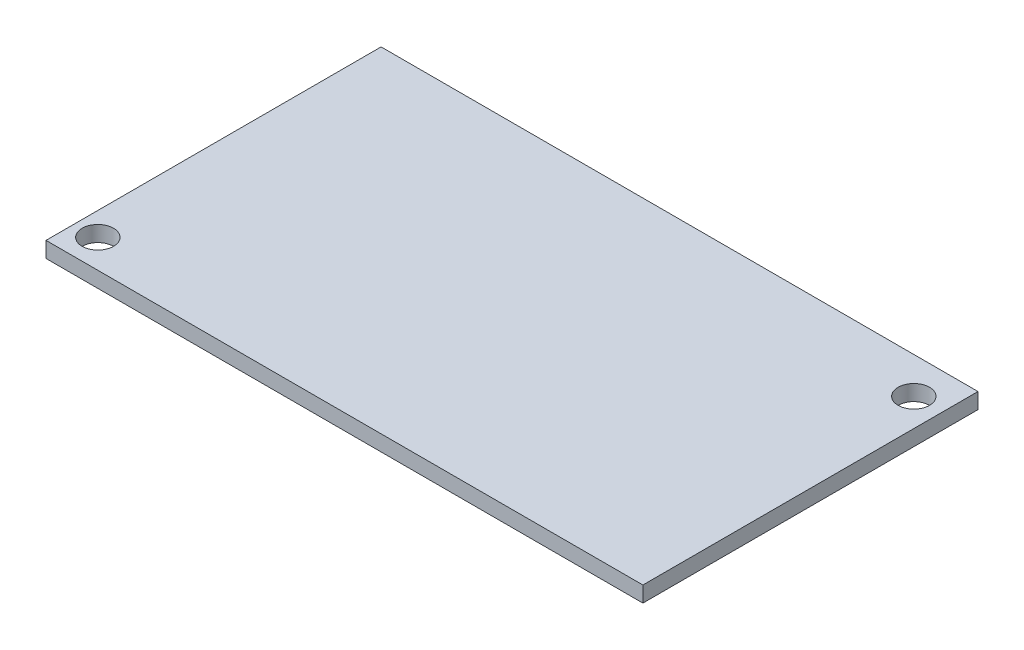
SolidWorks part; units mm, degrees
ref_plane "Front Plane" through (0, 0, 0) normal (0, 0, 1) x (1, 0, 0)
ref_plane "Top Plane" through (0, 0, 0) normal (0, 1, 0) x (1, 0, 0)
ref_plane "Right Plane" through (0, 0, 0) normal (1, 0, 0) x (0, 0, -1)
sketch "Sketch1" plane through (0, 0, 0) normal (0, 1, 0) x (1, 0, 0)
  line L1 (-28.5, 16) -> (28.5, 16)
  line L2 (-28.5, 16) -> (-28.5, -16)
  line L3 (-28.5, -16) -> (28.5, -16)
  line L4 (28.5, 16) -> (28.5, -16)
  line L5 (-28.5, 16) -> (28.5, -16) construction
  line L6 (-28.5, -16) -> (28.5, 16) construction
  point P0 (0, 0)
extrude "Boss-Extrude1" add sketch "Sketch1" along normal blind 1.5
sketch "Sketch2" plane through (0, 1.5, 0) normal (0, 1, 0) x (1, 0, 0)
  circle A0 centre (-26.2796, -13.2701) radius 1.5
  circle A1 centre (25.8321, 12.5372) radius 1.5
extrude "Cut-Extrude1" cut sketch "Sketch2" against normal through all
